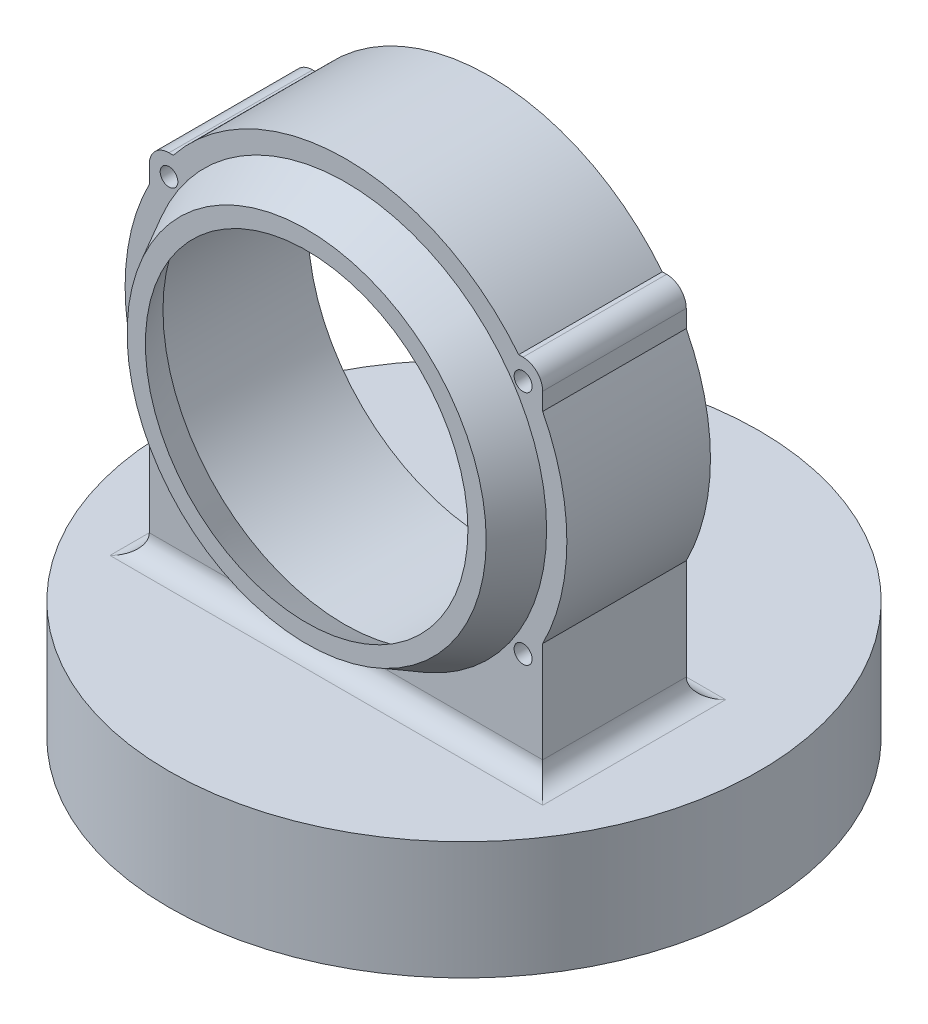
SolidWorks part; units mm, degrees
ref_plane "Alzado" through (0, 0, 0) normal (0, 0, 1) x (1, 0, 0)
ref_plane "Planta" through (0, 0, 0) normal (0, 1, 0) x (1, 0, 0)
ref_plane "Vista lateral" through (0, 0, 0) normal (1, 0, 0) x (0, 0, -1)
sketch "Croquis1" plane through (0, 0, 0) normal (0, 1, 0) x (1, 0, 0)
  circle A0 centre (0, 0) radius 75
  dimension "D1" = 150
extrude "Saliente-Extruir1" add sketch "Croquis1" along normal blind 30
sketch "Croquis3" plane through (0, 0, 0) normal (0, 0, 1) x (1, 0, 0)
  line L0 (43.907, 121.15) -> (45, 121.15)
  line L1 (50, 60.5996) -> (50, 30)
  line L2 (0, 0) -> (0, 85.4991) construction
  line L10 (-45, 121.15) -> (-43.907, 121.15)
  line L11 (-50, 116.15) -> (-50, 111.7004)
  line L12 (-50, 30) -> (50, 30)
  line L13 (50, 116.15) -> (50, 111.7004)
  line L14 (75, 30) -> (-75, 30) construction
  line L15 (-50, 60.5996) -> (-50, 30)
  circle A0 centre (0, 86.15) radius 46.15
  circle A1 centre (0, 86.15) radius 56.15
  arc A2 (45, 121.15) -> (50, 116.15) centre (45, 116.15) cw
  arc A3 (-45, 121.15) -> (-50, 116.15) centre (-45, 116.15) ccw
  point P5 (-0.8152, 30)
  point P17 (50, 121.15)
  point P20 (-50, 121.15)
  dimension "D4" = 92.3
  dimension "D6" = 5
  dimension "D1" = 100
  dimension "D2" = 10
  dimension "D3" = 35
  dimension "D5" = 50
extrude "Saliente-Extruir2" add sketch "Croquis3" against normal blind 36.5 from offset 30 contours A1 L15 L12 | A1 L12 L1 | L10 A3 L11 A1 | A2 L0 A1 L13 | A1 | A0 region at (47.8302, 117.6386, 0) region at (-47.8302, 117.6386, 0) region at (38.2791, 38.5026, 0) region at (-38.2791, 38.5026, 0)
sketch "Croquis5" plane through (0, 0, 30) normal (0, 0, 1) x (1, 0, 0)
  circle A0 centre (0, 86.15) radius 41
  circle A1 centre (0, 86.15) radius 51
  circle A2 centre (0, 86.15) radius 46.15 construction
  circle A3 centre (0, 86.15) radius 46.15 construction
  dimension "D1" = 82
  dimension "D2" = 10
extrude "Saliente-Extruir3" add sketch "Croquis5" along normal blind 10
chamfer "Chaflán1" distance 10 angle 28.15 1 edges at (41, 86.15, 30) first distance on face at (41, 86.15, 40)
chamfer "Chaflán2" distance 10 angle 28.15 1 edges at (51, 86.15, 40) first distance on face at (51, 86.15, 40)
fillet "Redondeo1" radius 5 4 edges at (0, 30, -6.5) (-50, 30, 11.75) (0, 30, 30) (50, 30, 11.75)
sketch "Croquis7" plane through (0, 0, -6.5) normal (0, 0, -1) x (-1, 0, 0)
  line L0 (0, 85.85) -> (71.2114, 85.85) construction
  circle A0 centre (44.9882, 115.8636) radius 2.2483
  circle A1 centre (-45.0262, 115.8636) radius 2.2831
  circle A2 centre (-45.0262, 55.8364) radius 2.2831
  circle A3 centre (44.9882, 55.8364) radius 2.2483
  dimension "D3" = 4.4965
  dimension "D1" = 30.0136
  dimension "D2" = 44.9882
extrude "Cortar-Extruir2" cut sketch "Croquis7" against normal through all
sketch "Croquis8" plane through (0, 0, 0) normal (0, -1, 0) x (1, 0, 0)
  circle A0 centre (0, 0) radius 61.2271
  circle A1 centre (-26.6444, -9.8249) radius 2.5
  circle A2 centre (8.1267, 27.2104) radius 2.5
  circle A3 centre (26.6444, 9.8249) radius 2.5
  circle A4 centre (-8.1267, -27.2104) radius 2.5
  dimension "D1" = 122.4541
  dimension "D2" = 5
extrude "Cortar-Extruir3" cut sketch "Croquis8" against normal blind 1.5 contours A0
extrude "Cortar-Extruir4" cut sketch "Croquis8<3>" against normal blind 10 contours A1 | A2 | A3 | A4
sketch "Croquis8<3>" plane through (0, 0, 0) normal (0, -1, 0) x (1, 0, 0) same geometry as "Croquis8"
